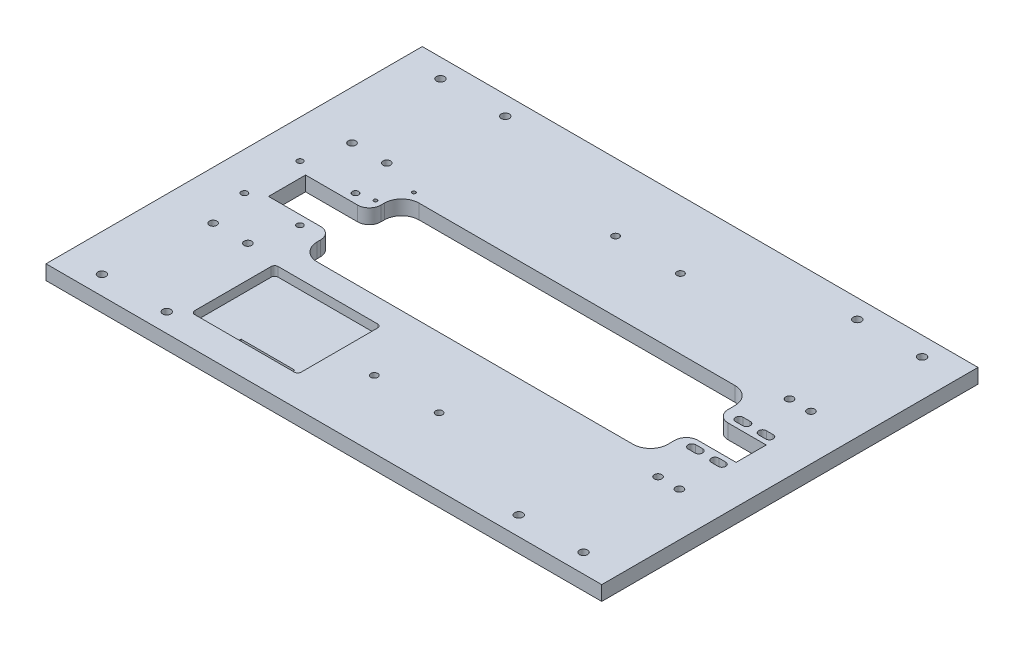
SolidWorks part; units mm, degrees
ref_plane "Front Plane" through (0, 0, 0) normal (0, 0, 1) x (1, 0, 0)
ref_plane "Top Plane" through (0, 0, 0) normal (0, 1, 0) x (1, 0, 0)
ref_plane "Right Plane" through (0, 0, 0) normal (1, 0, 0) x (0, 0, -1)
sketch "Sketch1" plane through (0, 0, 0) normal (0, 1, 0) x (1, 0, 0)
  line L1 (-240, 162.5) -> (240, 162.5)
  line L2 (-240, 162.5) -> (-240, -162.5)
  line L3 (-240, -162.5) -> (240, -162.5)
  line L4 (240, 162.5) -> (240, -162.5)
  line L5 (-240, 162.5) -> (240, -162.5) construction
  line L6 (-240, -162.5) -> (240, 162.5) construction
  point P0 (0, 0)
  dimension "D1" = 480
  dimension "D2" = 325
extrude "Boss-Extrude1" add sketch "Sketch1" along normal blind 12.6
sketch "Sketch2" plane through (0, 0, 0) normal (0, -1, 0) x (1, 0, 0)
  circle A0 centre (41.2474, -104.2) radius 3
  circle A1 centre (-14.7526, -104.2) radius 3
  circle A2 centre (41.2474, 104.2) radius 3
  circle A3 centre (-14.7526, 104.2) radius 3
extrude "Cut-Extrude1" cut sketch "Sketch2" against normal up to next
sketch "Sketch3" plane through (0, 0, 0) normal (0, -1, 0) x (1, 0, 0)
  line L0 (-192.4406, 0) -> (188.5847, 0) construction
  line L1 (163.5847, 44) -> (-139.2887, 44)
  line L2 (163.5847, 44) -> (163.5847, 13)
  line L3 (163.5847, -44) -> (-139.2887, -44)
  line L5 (-139.2887, -44) -> (-139.2887, -16)
  line L6 (-139.2887, -16) -> (-194.2887, -16)
  line L7 (-139.2887, 44) -> (-139.2887, 16)
  line L8 (-139.2887, 16) -> (-194.2887, 16)
  line L9 (-194.2887, 16) -> (-194.2887, -16)
  line L10 (163.5847, 13) -> (206.5847, 13)
  line L11 (206.5847, 13) -> (206.5847, -13)
  line L12 (206.5847, -13) -> (163.5847, -13)
  line L13 (163.5847, -13) -> (163.5847, -44)
  point P0 (0, 0)
  point P1 (-194.2887, 0)
  point P4 (-139.2887, -30)
  dimension "D2" = 55
  dimension "D1" = 16
  dimension "D3" = 13
  dimension "D4" = 13
  dimension "D5" = 43
  dimension "D6" = 28
  dimension "D7" = 28
extrude "Cut-Extrude2" cut sketch "Sketch3" against normal up to next
fillet "Fillet1" radius 10 2 edges at (-139.2887, 6.3, 16) (-139.2887, 6.3, -16)
sketch "Sketch4" plane through (0, 0, 0) normal (0, -1, 0) x (1, 0, 0)
  circle A0 centre (-159.1757, 24) radius 2.6185
  circle A1 centre (-207.1757, 24) radius 2.7
  circle A2 centre (-207.1757, -24) radius 2.5
  circle A3 centre (-159.1757, -24) radius 2.7
  circle A4 centre (-168.1757, -60.0027) radius 3.25
  circle A5 centre (-198.1757, -60.0027) radius 3.25
  circle A6 centre (-168.1757, 60) radius 3.25
  circle A7 centre (-198.1757, 60) radius 3.25
  point P24 (0, 0)
extrude "Cut-Extrude3" cut sketch "Sketch4" against normal up to next
fillet "Fillet2" radius 10 2 edges at (163.5847, 6.3, -13) (163.5847, 6.3, 13)
sketch "Sketch5" plane through (0, 0, 0) normal (0, -1, 0) x (1, 0, 0)
  circle A0 centre (183.6248, 57.5) radius 3.25 construction
  circle A1 centre (202.1353, 57.5) radius 3.25 construction
  circle A2 centre (200.7163, -57.5) radius 3.25 construction
  circle A3 centre (182.2059, -57.5) radius 3.25 construction
  circle A4 centre (183.6248, 57.5) radius 3.25
  circle A5 centre (202.1353, 57.5) radius 3.25
  circle A6 centre (200.7163, -57.5) radius 3.25
  circle A7 centre (182.2059, -57.5) radius 3.25
extrude "Cut-Extrude4" cut sketch "Sketch5" against normal blind 2
extrude "Cut-Extrude5" cut sketch "Sketch5<2>" against normal up to next
sketch "Sketch5<2>" plane through (0, 0, 0) normal (0, -1, 0) x (1, 0, 0) same geometry as "Sketch5"
sketch "Sketch6" plane through (0, 0, 0) normal (0, -1, 0) x (1, 0, 0)
  line L0 (192.6141, -20.5) -> (188.5112, -20.5) construction
  line L1 (192.6141, 20.5) -> (188.5112, 20.5) construction
  line L2 (201.8641, -23.75) -> (195.8641, -23.75)
  line L3 (201.8641, -17.25) -> (195.8641, -17.25)
  line L6 (201.8641, 17.25) -> (195.8641, 17.25)
  line L7 (201.8641, 23.75) -> (195.8641, 23.75)
  line L8 (181.8641, 17.25) -> (175.8641, 17.25)
  line L10 (176.0112, -20.5) -> (171.8318, -20.5) construction
  line L11 (181.8641, 23.75) -> (175.8641, 23.75)
  line L12 (176.0112, -20.5) -> (182.0112, -20.5) construction
  line L13 (175.8641, -23.75) -> (182.0112, -23.75)
  line L14 (175.8641, -17.25) -> (182.0112, -17.25)
  arc A0 (201.8641, -23.75) -> (201.8641, -17.25) centre (201.8641, -20.5) ccw
  arc A3 (201.8641, 17.25) -> (201.8641, 23.75) centre (201.8641, 20.5) ccw
  arc A4 (195.8641, -17.25) -> (195.8641, -23.75) centre (195.8641, -20.5) ccw
  arc A8 (175.8641, -17.25) -> (175.8641, -23.75) centre (175.8641, -20.5) ccw
  arc A9 (181.8641, 17.25) -> (181.8641, 23.75) centre (181.8641, 20.5) ccw
  arc A10 (195.8641, 23.75) -> (195.8641, 17.25) centre (195.8641, 20.5) ccw
  arc A11 (175.8641, 23.75) -> (175.8641, 17.25) centre (175.8641, 20.5) ccw
  arc A12 (182.0112, -23.75) -> (182.0112, -17.25) centre (182.0112, -20.5) ccw
  dimension "D2" = 6.5
  dimension "D3" = 6
  dimension "D5" = 3.25
  dimension "D7" = 6.5
  dimension "D1" = 6
  dimension "D4" = 6
  dimension "D6" = 6
extrude "Cut-Extrude6" cut sketch "Sketch6" against normal up to next and the other way blind 2
sketch "Sketch7" plane through (0, 12.6, 0) normal (0, 1, 0) x (1, 0, 0)
  circle A0 centre (208, -146.2) radius 2.25
  circle A1 centre (152, -146.2) radius 2.25
  circle A2 centre (-152, -146.2) radius 2.25
  circle A3 centre (-208, -146.2) radius 2.25
  circle A4 centre (-208, 146.2) radius 2.25
  circle A5 centre (-152, 146.2) radius 2.25
  circle A6 centre (208, 146.2) radius 2.25
  circle A7 centre (152, 146.2) radius 2.25
  dimension "D1" = 4.5
extrude "Cut-Extrude7" cut sketch "Sketch7" against normal up to next
sketch "Sketch8" plane through (0, 12.6, 0) normal (0, 1, 0) x (1, 0, 0)
  circle A0 centre (208, 146.2) radius 3.5
  circle A1 centre (152, 146.2) radius 3.5
  circle A2 centre (-152, 146.2) radius 3.5
  circle A3 centre (-208, 146.2) radius 3.5
  circle A4 centre (208, -146.2) radius 3.5
  circle A5 centre (152, -146.2) radius 3.5
  circle A6 centre (-208, -146.2) radius 3.5
  circle A7 centre (-152, -146.2) radius 3.5
  dimension "D1" = 7
extrude "Cut-Extrude8" cut sketch "Sketch8" against normal blind 6
sketch "Sketch9" plane through (0, 12.6, 0) normal (0, 1, 0) x (1, 0, 0)
  line L0 (-139.7386, -65.278) -> (-139.7386, -135.278) construction
  line L1 (-137.7386, -64.278) -> (-51.7386, -64.278)
  line L2 (-140.7386, -67.278) -> (-140.7386, -133.278)
  line L3 (-137.7386, -136.278) -> (-51.7386, -136.278)
  line L4 (-48.7386, -67.278) -> (-48.7386, -133.278)
  line L5 (-49.7386, -135.278) -> (-49.7386, -65.278) construction
  line L6 (-49.7386, -65.278) -> (-139.7386, -65.278) construction
  line L7 (-139.7386, -135.278) -> (-49.7386, -135.278) construction
  arc A0 (-140.7386, -133.278) -> (-137.7386, -136.278) centre (-137.7386, -133.278) ccw
  arc A1 (-51.7386, -136.278) -> (-48.7386, -133.278) centre (-51.7386, -133.278) ccw
  arc A2 (-51.7386, -64.278) -> (-48.7386, -67.278) centre (-51.7386, -67.278) cw
  arc A3 (-137.7386, -64.278) -> (-140.7386, -67.278) centre (-137.7386, -67.278) ccw
  dimension "D5" = 3
  dimension "D1" = 1
  dimension "D2" = 1
  dimension "D3" = 1
  dimension "D4" = 1
extrude "Cut-Extrude9" cut sketch "Sketch9" against normal blind 8
sketch "Sketch10" plane through (0, 4.6, 0) normal (0, 1, 0) x (1, 0, 0)
  line L1 (-107.3842, -126.6207) -> (-60.9487, -126.6207)
  line L2 (-107.3842, -126.6207) -> (-107.3842, -133.6207)
  line L3 (-107.3842, -133.6207) -> (-60.9487, -133.6207)
  line L4 (-60.9487, -126.6207) -> (-60.9487, -133.6207)
  dimension "D1" = 7
extrude "Cut-Extrude10" cut sketch "Sketch10" against normal up to next
sketch "Sketch12" plane through (0, 0, 0) normal (0, -1, 0) x (1, 0, 0)
  circle A0 centre (-145.0986, -27.142) radius 1.5
  circle A1 centre (-134.4986, -49.742) radius 1.5
extrude "Cut-Extrude11" cut sketch "Sketch12" against normal up to next
sketch "Sketch13" plane through (0, 0, 0) normal (0, 1, 0) x (1, 0, 0)
  line L2 (201.8641, 23.75) -> (195.8641, 23.75)
  line L3 (195.8641, 17.25) -> (201.8641, 17.25)
  line L4 (240, -162.5) -> (240, 162.5)
  line L5 (240, 162.5) -> (-240, 162.5)
  line L6 (-240, 162.5) -> (-240, -162.5)
  line L7 (-240, -162.5) -> (240, -162.5)
  line L8 (240, -162.5) -> (240, 162.5)
  line L9 (240, 162.5) -> (-240, 162.5)
  line L10 (-240, 162.5) -> (-240, -162.5)
  line L11 (-240, -162.5) -> (240, -162.5)
  line L12 (201.8641, 23.75) -> (195.8641, 23.75)
  line L13 (195.8641, 17.25) -> (201.8641, 17.25)
  line L14 (201.8641, -17.25) -> (195.8641, -17.25)
  line L15 (195.8641, -23.75) -> (201.8641, -23.75)
  line L16 (201.8641, -17.25) -> (195.8641, -17.25)
  line L17 (195.8641, -23.75) -> (201.8641, -23.75)
  line L18 (163.5847, 23) -> (163.5847, 44)
  line L19 (206.5847, 13) -> (173.5847, 13)
  line L20 (206.5847, -13) -> (206.5847, 13)
  line L21 (173.5847, -13) -> (206.5847, -13)
  line L22 (163.5847, -44) -> (163.5847, -23)
  line L23 (-139.2887, -44) -> (163.5847, -44)
  line L24 (-194.2887, -16) -> (-149.2887, -16)
  line L25 (-194.2887, 16) -> (-194.2887, -16)
  line L26 (-149.2887, 16) -> (-194.2887, 16)
  line L27 (163.5847, 44) -> (-139.2887, 44)
  line L28 (163.5847, 23) -> (163.5847, 44)
  line L29 (206.5847, 13) -> (173.5847, 13)
  line L30 (206.5847, -13) -> (206.5847, 13)
  line L31 (173.5847, -13) -> (206.5847, -13)
  line L32 (163.5847, -44) -> (163.5847, -23)
  line L33 (-139.2887, -44) -> (163.5847, -44)
  line L34 (-194.2887, -16) -> (-149.2887, -16)
  line L35 (-194.2887, 16) -> (-194.2887, -16)
  line L36 (-149.2887, 16) -> (-194.2887, 16)
  line L37 (163.5847, 44) -> (-139.2887, 44)
  line L38 (181.8641, -17.25) -> (175.8641, -17.25)
  line L39 (175.8641, -23.75) -> (181.8641, -23.75)
  line L40 (181.8641, -17.25) -> (175.8641, -17.25)
  line L42 (182.0112, 23.75) -> (175.8641, 23.75)
  line L43 (182.0112, 23.75) -> (175.8641, 23.75)
  line L46 (175.8641, -23.75) -> (181.8641, -23.75)
  line L47 (175.8641, 17.25) -> (182.0112, 17.25)
  line L48 (175.8641, 17.25) -> (182.0112, 17.25)
  line L50 (-137.7386, -136.278) -> (-51.7386, -136.278)
  line L51 (-48.7386, -133.278) -> (-48.7386, -67.278)
  line L52 (-51.7386, -64.278) -> (-137.7386, -64.278)
  line L53 (-140.7386, -67.278) -> (-140.7386, -133.278)
  line L54 (-137.7386, -136.278) -> (-51.7386, -136.278)
  line L55 (-48.7386, -133.278) -> (-48.7386, -67.278)
  line L56 (-51.7386, -64.278) -> (-137.7386, -64.278)
  line L57 (-140.7386, -67.278) -> (-140.7386, -133.278)
  line L58 (-107.3842, -126.6207) -> (-107.3842, -133.6207)
  line L59 (-60.9487, -126.6207) -> (-107.3842, -126.6207)
  line L60 (-60.9487, -133.6207) -> (-60.9487, -126.6207)
  line L61 (-107.3842, -133.6207) -> (-60.9487, -133.6207)
  line L62 (-107.3842, -126.6207) -> (-107.3842, -133.6207)
  line L63 (-60.9487, -126.6207) -> (-107.3842, -126.6207)
  line L64 (-60.9487, -133.6207) -> (-60.9487, -126.6207)
  line L65 (-107.3842, -133.6207) -> (-60.9487, -133.6207)
  line L72 (-139.2887, -26) -> (-139.2887, -44)
  line L73 (-139.2887, -26) -> (-139.2887, -44)
  line L74 (-139.2887, 44) -> (-139.2887, 26)
  line L75 (-139.2887, 44) -> (-139.2887, 26)
  circle A0 centre (202.1353, -57.5) radius 3.25 construction
  circle A1 centre (183.6248, -57.5) radius 3.25 construction
  arc A2 (201.8641, 17.25) -> (201.8641, 23.75) centre (201.8641, 20.5) ccw
  arc A3 (195.8641, 23.75) -> (195.8641, 17.25) centre (195.8641, 20.5) ccw
  arc A4 (163.5847, 23) -> (173.5847, 13) centre (173.5847, 23) ccw
  arc A5 (173.5847, -13) -> (163.5847, -23) centre (173.5847, -23) ccw
  arc A6 (-139.2887, -26) -> (-149.2887, -16) centre (-149.2887, -26) ccw
  arc A7 (-149.2887, 16) -> (-139.2887, 26) centre (-149.2887, 26) ccw
  arc A8 (163.5847, 23) -> (173.5847, 13) centre (173.5847, 23) ccw
  arc A9 (173.5847, -13) -> (163.5847, -23) centre (173.5847, -23) ccw
  arc A10 (-139.2887, -26) -> (-149.2887, -16) centre (-149.2887, -26) ccw
  arc A11 (-149.2887, 16) -> (-139.2887, 26) centre (-149.2887, 26) ccw
  arc A12 (201.8641, 17.25) -> (201.8641, 23.75) centre (201.8641, 20.5) ccw
  arc A13 (195.8641, 23.75) -> (195.8641, 17.25) centre (195.8641, 20.5) ccw
  arc A14 (201.8641, -23.75) -> (201.8641, -17.25) centre (201.8641, -20.5) ccw
  arc A15 (195.8641, -17.25) -> (195.8641, -23.75) centre (195.8641, -20.5) ccw
  arc A16 (201.8641, -23.75) -> (201.8641, -17.25) centre (201.8641, -20.5) ccw
  arc A17 (195.8641, -17.25) -> (195.8641, -23.75) centre (195.8641, -20.5) ccw
  arc A18 (181.8641, -23.75) -> (181.8641, -17.25) centre (181.8641, -20.5) ccw
  arc A19 (175.8641, -17.25) -> (175.8641, -23.75) centre (175.8641, -20.5) ccw
  arc A20 (181.8641, -23.75) -> (181.8641, -17.25) centre (181.8641, -20.5) ccw
  arc A22 (182.0112, 17.25) -> (182.0112, 23.75) centre (182.0112, 20.5) ccw
  arc A23 (175.8641, 23.75) -> (175.8641, 17.25) centre (175.8641, 20.5) ccw
  arc A25 (175.8641, 23.75) -> (175.8641, 17.25) centre (175.8641, 20.5) ccw
  circle A26 centre (182.2059, 57.5) radius 3.25 construction
  circle A27 centre (200.7163, 57.5) radius 3.25 construction
  circle A28 centre (152, -146.2) radius 2.25 construction
  circle A29 centre (152, -146.2) radius 3.5 construction
  circle A30 centre (208, -146.2) radius 2.25 construction
  circle A31 centre (208, -146.2) radius 3.5 construction
  circle A32 centre (41.2474, -104.2) radius 3 construction
  circle A33 centre (-14.7526, -104.2) radius 3 construction
  circle A34 centre (-152, -146.2) radius 2.25 construction
  circle A35 centre (-152, -146.2) radius 3.5 construction
  circle A36 centre (-208, -146.2) radius 2.25 construction
  circle A37 centre (-208, -146.2) radius 3.5 construction
  circle A38 centre (-198.1757, -60) radius 3.25 construction
  circle A39 centre (-168.1757, -60) radius 3.25 construction
  circle A40 centre (-168.1757, -60) radius 3.25
  circle A41 centre (-198.1757, -60) radius 3.25
  circle A42 centre (-208, -146.2) radius 3.5
  circle A43 centre (-208, -146.2) radius 2.25
  circle A44 centre (-152, -146.2) radius 3.5
  circle A45 centre (-152, -146.2) radius 2.25
  circle A46 centre (-14.7526, -104.2) radius 3
  circle A47 centre (41.2474, -104.2) radius 3
  circle A48 centre (208, -146.2) radius 3.5
  circle A49 centre (208, -146.2) radius 2.25
  circle A50 centre (152, -146.2) radius 3.5
  circle A51 centre (152, -146.2) radius 2.25
  circle A52 centre (200.7163, 57.5) radius 3.25
  circle A53 centre (182.2059, 57.5) radius 3.25
  circle A54 centre (183.6248, -57.5) radius 3.25
  circle A55 centre (202.1353, -57.5) radius 3.25
  circle A56 centre (208, 146.2) radius 3.5 construction
  circle A57 centre (208, 146.2) radius 2.25 construction
  circle A58 centre (152, 146.2) radius 3.5 construction
  circle A59 centre (152, 146.2) radius 2.25 construction
  circle A60 centre (41.2474, 104.2) radius 3 construction
  circle A61 centre (-14.7526, 104.2) radius 3 construction
  circle A62 centre (-152, 146.2) radius 3.5 construction
  circle A63 centre (-152, 146.2) radius 2.25 construction
  circle A64 centre (-208, 146.2) radius 3.5 construction
  circle A65 centre (-208, 146.2) radius 2.25 construction
  circle A66 centre (-198.1757, 60.0027) radius 3.25 construction
  circle A67 centre (-168.1757, 60.0027) radius 3.25 construction
  circle A68 centre (-134.4986, 49.742) radius 1.5 construction
  circle A69 centre (-145.0986, 27.142) radius 1.5 construction
  circle A70 centre (-159.1757, 24) radius 2.7 construction
  circle A71 centre (-207.1757, 24) radius 2.5 construction
  circle A72 centre (-207.1757, -24) radius 2.7 construction
  circle A73 centre (-159.1757, -24) radius 2.6185 construction
  circle A74 centre (208, 146.2) radius 3.5
  circle A75 centre (208, 146.2) radius 2.25
  circle A76 centre (152, 146.2) radius 3.5
  circle A77 centre (152, 146.2) radius 2.25
  circle A78 centre (41.2474, 104.2) radius 3
  circle A79 centre (-14.7526, 104.2) radius 3
  circle A80 centre (-152, 146.2) radius 3.5
  circle A81 centre (-152, 146.2) radius 2.25
  circle A82 centre (-208, 146.2) radius 3.5
  circle A83 centre (-208, 146.2) radius 2.25
  circle A84 centre (-198.1757, 60.0027) radius 3.25
  circle A85 centre (-168.1757, 60.0027) radius 3.25
  circle A86 centre (-134.4986, 49.742) radius 1.5
  circle A87 centre (-145.0986, 27.142) radius 1.5
  circle A88 centre (-159.1757, 24) radius 2.7
  circle A89 centre (-207.1757, 24) radius 2.5
  circle A90 centre (-207.1757, -24) radius 2.7
  circle A91 centre (-159.1757, -24) radius 2.6185
  arc A94 (175.8641, -17.25) -> (175.8641, -23.75) centre (175.8641, -20.5) ccw
  arc A95 (182.0112, 17.25) -> (182.0112, 23.75) centre (182.0112, 20.5) ccw
  arc A96 (-140.7386, -133.278) -> (-137.7386, -136.278) centre (-137.7386, -133.278) ccw
  arc A97 (-51.7386, -136.278) -> (-48.7386, -133.278) centre (-51.7386, -133.278) ccw
  arc A98 (-48.7386, -67.278) -> (-51.7386, -64.278) centre (-51.7386, -67.278) ccw
  arc A99 (-137.7386, -64.278) -> (-140.7386, -67.278) centre (-137.7386, -67.278) ccw
  arc A100 (-140.7386, -133.278) -> (-137.7386, -136.278) centre (-137.7386, -133.278) ccw
  arc A101 (-51.7386, -136.278) -> (-48.7386, -133.278) centre (-51.7386, -133.278) ccw
  arc A102 (-48.7386, -67.278) -> (-51.7386, -64.278) centre (-51.7386, -67.278) ccw
  arc A103 (-137.7386, -64.278) -> (-140.7386, -67.278) centre (-137.7386, -67.278) ccw
  dimension "D1" = 0
  dimension "D2" = 0
  dimension "D3" = 0
  dimension "D4" = 0
  dimension "D5" = 0
  dimension "D6" = 0
  dimension "D7" = 0
  dimension "D8" = 0
fillet "Fillet3" radius 15 4 edges at (163.5847, 6.3, 44) (163.5847, 6.3, -44) (-139.2887, 6.3, 44) (-139.2887, 6.3, -44)
